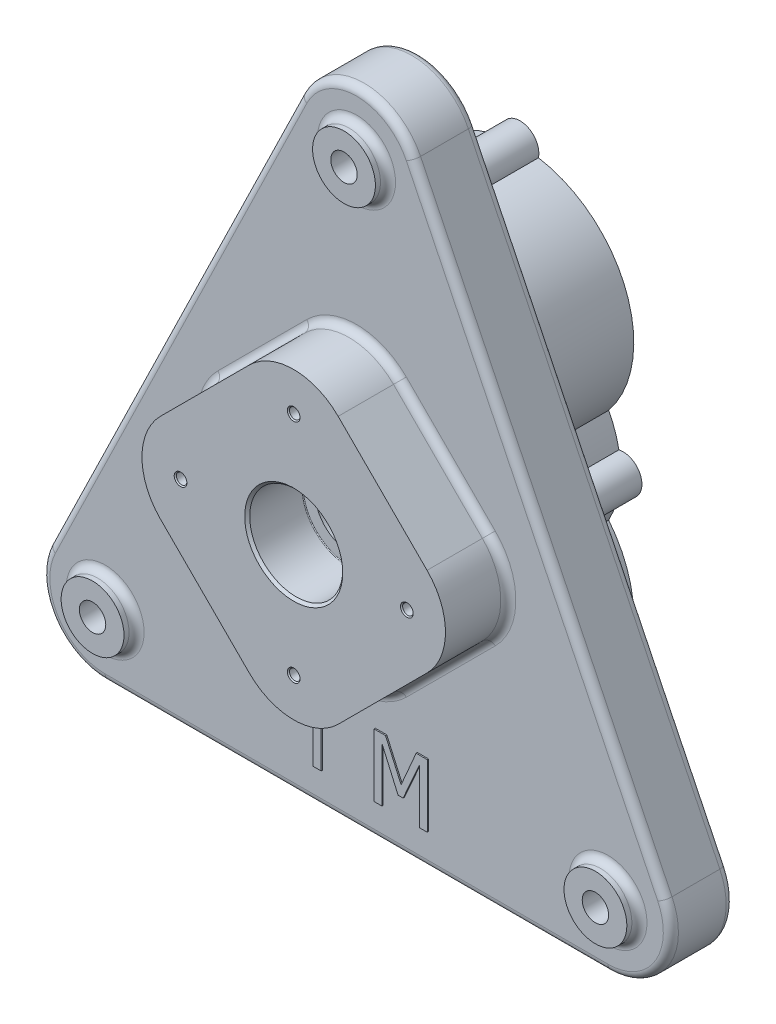
SolidWorks part; units mm, degrees
material "Cast Alloy Steel"
ref_plane "Front Plane" through (0, 0, 0) normal (0, 0, 1) x (1, 0, 0)
ref_plane "Top Plane" through (0, 0, 0) normal (0, 1, 0) x (1, 0, 0)
ref_plane "Right Plane" through (0, 0, 0) normal (1, 0, 0) x (0, 0, -1)
sketch "Sketch1" plane through (0, 0, 0) normal (0, 0, 1) x (1, 0, 0)
  line L0 (0, 120) -> (0, -143.1186) construction
  line L1 (-150.0941, 0) -> (143.2063, 0) construction
  line L2 (53.033, -17.6777) -> (17.6777, -53.033)
  line L3 (53.033, 17.6777) -> (17.6777, 53.033)
  line L4 (-17.6777, -53.033) -> (-53.033, -17.6777)
  line L5 (-17.6777, 53.033) -> (-53.033, 17.6777)
  line L6 (70.7107, 0) -> (-70.7107, 0) construction
  line L7 (0, -70.7107) -> (0, 70.7107) construction
  line L8 (-22.4692, 130.9606) -> (-122.4692, -74.0394)
  line L9 (-100, -110) -> (100, -110)
  line L10 (122.4692, -74.0394) -> (22.4692, 130.9606)
  circle A0 centre (0, 0) radius 13.5
  circle A1 centre (0, 120) radius 12.5
  circle A3 centre (-100, -85) radius 12.5
  circle A4 centre (100, -85) radius 12.5
  arc A5 (22.4692, 130.9606) -> (-22.4692, 130.9606) centre (0, 120) ccw
  arc A6 (-122.4692, -74.0394) -> (-100, -110) centre (-100, -85) ccw
  arc A7 (100, -110) -> (122.4692, -74.0394) centre (100, -85) ccw
  arc A8 (-53.033, -17.6777) -> (-53.033, 17.6777) centre (-35.3553, 0) cw
  arc A9 (17.6777, -53.033) -> (-17.6777, -53.033) centre (0, -35.3553) cw
  arc A10 (53.033, 17.6777) -> (53.033, -17.6777) centre (35.3553, 0) cw
  arc A11 (17.6777, 53.033) -> (-17.6777, 53.033) centre (0, 35.3553) ccw
  circle A12 centre (0, 120) radius 5.25
  circle A13 centre (-100, -85) radius 5.25
  circle A14 centre (100, -85) radius 5.25
  dimension "D1" = 25
  dimension "D7" = 27
  dimension "D8" = 50
  dimension "D9" = 25
  dimension "D10" = 10.5
  dimension "D2" = 120
  dimension "D3" = 205
  dimension "D4" = 100
  dimension "D5" = 100
  dimension "D6" = 100
extrude "Boss-Extrude1" add sketch "Sketch1" along normal blind 25 contours L9 A7 L10 A5 L8 A6 A11 L3 A10 L2 A9 L4 A8 L5 A4 A3 A1 | L3 A11 L5 A8 L4 A9 L2 A10 A0 | A4 A14 | A1 A12 | A3 A13 region at (34.1482, -34.1482, 0) region at (0, 141.4289, 0) region at (-12.1464, 120, 0) region at (-112.1464, -85, 0) region at (87.8536, -85, 0)
extrude "Boss-Extrude2" add sketch "Sketch1<3>" along normal blind 50 contours L3 A11 L5 A8 L4 A9 L2 A10 A0 region at (34.1482, -34.1482, 0)
sketch "Sketch1<3>" plane through (0, 0, 0) normal (0, 0, 1) x (1, 0, 0) same geometry as "Sketch1"
sketch "Sketch2" plane through (0, 0, 0) normal (0, 0, -1) x (-1, 0, 0)
  line L0 (0, 145) -> (0, -110) construction
  line L1 (100, -110) -> (-100, -110) construction
  line L2 (-86.3524, 0) -> (86.3524, 0) construction
  line L3 (-122.4692, -74.0394) -> (-22.4692, 130.9606) construction
  line L4 (22.4692, 130.9606) -> (122.4692, -74.0394) construction
  arc A0 (22.4692, 130.9606) -> (-22.4692, 130.9606) centre (0, 120) ccw construction
  arc A1 (-28.1448, 12.9949) -> (-28.1448, -12.9949) centre (0, 0) ccw
  arc A2 (-32.4459, 13.125) -> (-32.4459, -13.125) centre (0, 0) ccw
  arc A3 (-35.2592, 18.8889) -> (-39.3262, 7.3108) centre (0, 0) ccw
  arc A4 (29.403, 26.0479) -> (-29.403, 26.0479) centre (0, 47.25) ccw
  arc A5 (33.634, 25.1408) -> (-33.634, 25.1408) centre (0, 47.25) ccw
  arc A6 (35.2592, 18.8889) -> (7.3279, 91.9027) centre (0, 47.25) ccw
  arc A7 (7.3279, 91.9027) -> (-7.3279, 91.9027) centre (0, 93.5) ccw
  arc A8 (-7.3279, 91.9027) -> (-35.2592, 18.8889) centre (0, 47.25) ccw
  arc A9 (29.403, -26.0479) -> (-29.403, -26.0479) centre (0, -47.25) cw
  arc A10 (33.634, -25.1408) -> (-33.634, -25.1408) centre (0, -47.25) cw
  arc A11 (35.2592, -18.8889) -> (7.3279, -91.9027) centre (0, -47.25) cw
  arc A12 (-7.3279, -91.9027) -> (-35.2592, -18.8889) centre (0, -47.25) cw
  arc A13 (7.3279, -91.9027) -> (-7.3279, -91.9027) centre (0, -93.5) cw
  arc A14 (28.1448, -12.9949) -> (28.1448, 12.9949) centre (0, 0) ccw
  arc A15 (32.4459, -13.125) -> (32.4459, 13.125) centre (0, 0) ccw
  arc A16 (35.2592, -18.8889) -> (39.3262, -7.3108) centre (0, 0) ccw
  arc A17 (-39.3262, 7.3108) -> (-39.3262, -7.3108) centre (-41, 0) ccw
  arc A18 (39.3262, 7.3108) -> (39.3262, -7.3108) centre (41, 0) cw
  arc A19 (-39.3262, -7.3108) -> (-35.2592, -18.8889) centre (0, 0) ccw
  arc A20 (39.3262, 7.3108) -> (35.2592, 18.8889) centre (0, 0) ccw
  arc A21 (33.634, -25.1408) -> (32.4459, -13.125) centre (44.4972, -18) cw
  arc A22 (29.403, -26.0479) -> (28.1448, -12.9949) centre (39.9475, -18.4444) cw
  arc A23 (32.4459, 13.125) -> (33.634, 25.1408) centre (44.4972, 18) cw
  arc A24 (29.403, 26.0479) -> (28.1448, 12.9949) centre (39.9475, 18.4444) ccw
  arc A25 (-33.634, -25.1408) -> (-32.4459, -13.125) centre (-44.4972, -18) ccw
  arc A26 (-29.403, -26.0479) -> (-28.1448, -12.9949) centre (-39.9475, -18.4444) ccw
  arc A27 (-33.634, 25.1408) -> (-32.4459, 13.125) centre (-44.4972, 18) cw
  arc A28 (-29.403, 26.0479) -> (-28.1448, 12.9949) centre (-39.9475, 18.4444) cw
  point P43 (29.1018, -19.4444)
  point P46 (23.7788, -19.8889)
  point P49 (29.1018, 19.4444)
  point P52 (23.7788, 19.8889)
  point P55 (-29.1018, -19.4444)
  point P58 (-23.7788, -19.8889)
  point P61 (-29.1018, 19.4444)
  point P64 (-23.7788, 19.8889)
  circle M31 centre (0, 0) radius 13.5
  dimension "D1" = 62
  dimension "D2" = 70
  dimension "D3" = 80
  dimension "D5" = 72.5
  dimension "D6" = 80.5
  dimension "D7" = 90.5
  dimension "D8" = 15
  dimension "D11" = 13
  dimension "D4" = 47.25
  dimension "D9" = 93.5
  dimension "D10" = 41
extrude "Boss-Extrude4" add sketch "Sketch2" along normal blind 40 contours A18 A20 A6 A7 A8 A3 A17 A19 A12 A13 A11 A16 A27 A5 A23 A15 A21 A10 A25 A2 region at (40.1702, 62.617, 0)
extrude "Boss-Extrude5" add sketch "Sketch2<6>" along normal blind 35 contours A5 A27 A2 A25 A10 A21 A15 A23 A28 A4 A24 A14 A22 A9 A26 A1 region at (29.6434, 19.4688, 0)
sketch "Sketch2<6>" plane through (0, 0, 0) normal (0, 0, -1) x (-1, 0, 0) same geometry as "Sketch2"
sketch "Sketch4" plane through (0, 0, 0) normal (0, 0, -1) x (-1, 0, 0)
  line L0 (0, 101) -> (0, -101) construction
  line L1 (-48.5, 0) -> (48.5, 0) construction
  circle A0 centre (0, 47.25) radius 15
  arc A1 (7.3279, 91.9027) -> (-7.3279, 91.9027) centre (0, 93.5) ccw construction
  arc A2 (-7.3279, -91.9027) -> (7.3279, -91.9027) centre (0, -93.5) ccw construction
  arc A3 (-39.3262, 7.3108) -> (-39.3262, -7.3108) centre (-41, 0) ccw construction
  arc A4 (39.3262, -7.3108) -> (39.3262, 7.3108) centre (41, 0) ccw construction
  circle A5 centre (0, 47.25) radius 12
  circle A6 centre (0, -47.25) radius 12
  circle A7 centre (0, -47.25) radius 15
  dimension "D1" = 30
  dimension "D2" = 24
extrude "Cut-Extrude6" cut sketch "Sketch2<7>" against normal blind 5 contours A4 A28 A1 A26 A9 A22 A14 A24 M31 region at (25.1953, 19.8664, 0)
sketch "Sketch2<7>" plane through (0, 0, 0) normal (0, 0, -1) x (-1, 0, 0) same geometry as "Sketch2"
extrude "Cut-Extrude7" cut sketch "Sketch4" against normal blind 20 contours A6 | A5 region at (0, 47.25, 0) region at (0, -47.25, 0)
extrude "Cut-Extrude8" cut sketch "Sketch4<5>" against normal blind 18 contours A0 A5 | A7 A6 region at (14.5757, 47.25, 0) region at (14.5757, -47.25, 0)
sketch "Sketch4<5>" plane through (0, 0, 0) normal (0, 0, -1) x (-1, 0, 0) same geometry as "Sketch4"
sketch "Sketch5" plane through (0, 0, 5) normal (0, 0, -1) x (-1, 0, 0)
  circle A0 centre (0, 0) radius 18.5
  dimension "D1" = 37
extrude "Cut-Extrude9" cut sketch "Sketch5" against normal blind 17
extrude "Cut-Extrude10" cut sketch "Sketch5<2>" along normal blind 22 from surface starting at face at (13.5, 0, 50)
sketch "Sketch5<2>" plane through (0, 0, 5) normal (0, 0, -1) x (-1, 0, 0) same geometry as "Sketch5"
fillet "Fillet1" radius 3 28 edges at (-27.0075, 19.6917, 5) (-31, 0, 5) (-27.0075, -19.6917, 5) (0, -83.5, 5) (27.0075, -19.6917, 5) (31, 0, 5) (27.0075, 19.6917, 5) (0, 60.3553, 25) (-35.3553, 35.3553, 25) (-60.3553, 0, 25) (-35.3553, -35.3553, 25) (0, -60.3553, 25) (35.3553, -35.3553, 25) (60.3553, 0, 25) (121.2016, -98.2474, 25) (0, -110, 25) (-121.2016, -98.2474, 25) (-72.4692, 28.4606, 25) (0, 145, 25) (121.2016, -98.2474, 0) (0, -110, 0) (-121.2016, -98.2474, 0) (-72.4692, 28.4606, 0) (0, 145, 0) (0, 83.5, 5) (35.3553, 35.3553, 25) (72.4692, 28.4606, 25) (72.4692, 28.4606, 0)
sketch "Sketch6" plane through (0, 0, 50) normal (0, 0, 1) x (1, 0, 0)
  circle A0 centre (0, 0) radius 45 construction
  circle A1 centre (0, 45) radius 3.6648
  circle A2 centre (45, 0) radius 3.6648
  circle A3 centre (0, -45) radius 3.6648
  circle A4 centre (-45, 0) radius 3.6648
  point P5 (-45, 0)
  point P14 (0, 0)
  dimension "D1" = 90
  dimension "D2" = 7.3295
  dimension "D3" = 4
hole_wizard "M5x0.8 Tapped Hole1" positions "3DSketch1" profile "Sketch7" tap size "M5x0.8" standard "ANSI Metric"
sketch3d "3DSketch1"
  point P0 (0, 45, 50)
  point P3 (-45, 0, 50)
  point P6 (45, 0, 50)
  point P9 (0, -45, 50)
sketch "Sketch7" plane through (0, 45, 50) normal (1, 0, 0) x (0, -1, 0)
  line L0 (0, 0) -> (0, 15)
  line L1 (0, 15) -> (2.1, 13.7382)
  line L2 (2.1, 13.7382) -> (2.1, 0.425)
  line L3 (2.1, 0.425) -> (2.525, 0)
  line L5 (2.525, 0) -> (0, 0)
  line L6 (-2.1, 0.425) -> (-2.525, 0) construction
  line L10 (0, 15) -> (-2.1, 13.7382) construction
  line L11 (0, -6.35) -> (0, 107.95) construction
  dimension "Tap Drill Dia." = 4.2
  dimension "Tap Drill Depth" = 15
  dimension "Near C'Sink Dia." = 5.05
  dimension "Near C'Sink Angle" = 90
  dimension "Drill Angle" = 118
cosmetic thread "Hole Thread1" parameters "D1"=13, "D2"=5
cosmetic thread "Hole Thread2" parameters "D1"=13, "D2"=5
cosmetic thread "Hole Thread3" parameters "D1"=13, "D2"=5
cosmetic thread "Hole Thread4" parameters "D1"=13, "D2"=5
sketch "Sketch8" plane through (0, 0, -40) normal (0, 0, -1) x (-1, 0, 0)
  circle A0 centre (0, 93.5) radius 2.5
  circle A1 centre (41, 0) radius 2.5
  circle A2 centre (-41, 0) radius 2.5
  circle A3 centre (0, -93.5) radius 2.5
  point P12 (-41, 0)
  point P13 (-41, 0)
  dimension "D1" = 5
  dimension "D2" = 5
hole_wizard "M6x1.0 Tapped Hole1" positions "3DSketch2" profile "Sketch9" tap size "M6x1.0" standard "ANSI Metric"
sketch3d "3DSketch2"
  point P0 (0, 93.5, -40)
  point P3 (-41, 0, -40)
  point P6 (41, 0, -40)
  point P9 (0, -93.5, -40)
sketch "Sketch9" plane through (0, 93.5, -40) normal (1, 0, 0) x (0, 1, 0)
  line L0 (0, 0) -> (0, 22)
  line L1 (0, 22) -> (2.5, 20.4978)
  line L2 (2.5, 20.4978) -> (2.5, 0.525)
  line L3 (2.5, 0.525) -> (3.025, 0)
  line L5 (3.025, 0) -> (0, 0)
  line L6 (-2.5, 0.525) -> (-3.025, 0) construction
  line L10 (0, 22) -> (-2.5, 20.4978) construction
  line L11 (0, -6.35) -> (0, 107.95) construction
  dimension "Tap Drill Dia." = 5
  dimension "Tap Drill Depth" = 22
  dimension "Near C'Sink Dia." = 6.05
  dimension "Near C'Sink Angle" = 90
  dimension "Drill Angle" = 118
cosmetic thread "Hole Thread5" parameters "D1"=20, "D2"=6
cosmetic thread "Hole Thread6" parameters "D1"=20, "D2"=6
cosmetic thread "Hole Thread7" parameters "D1"=20, "D2"=6
cosmetic thread "Hole Thread8" parameters "D1"=20, "D2"=6
fillet "Fillet3" radius 2 12 edges at (37.7393, -13.2568, 0) (37.7393, 13.2568, 0) (48.5, 0, 0) (0, 101, 0) (42.2631, 63.4176, 0) (-37.7393, -13.2568, 0) (-37.7393, 13.2568, 0) (-42.2631, 63.4176, 0) (-48.5, 0, 0) (0, -101, 0) (42.2631, -63.4176, 0) (-42.2631, -63.4176, 0)
chamfer "Chamfer1" distance 1 angle 45 4 edges at (18.5, 0, 50) (-15, -47.25, 5) (-15, 47.25, 5) (-18.5, 0, 5)
sketch "Sketch10" plane through (0, 0, 25) normal (0, 0, 1) x (1, 0, 0)
  line L0 (-100, -107) -> (100, -107) construction
  text T0 "TM" font "Tahoma" height 25
  point P1 (-28.3234, -87.0645)
  point P2 (-27.0426, -90.5865)
  dimension "D1" = 10
  dimension "D2" = 25
extrude "Boss-Extrude6" add sketch "Sketch10" along normal blind 0.5
sketch "Sketch11" plane through (0, 0, 25) normal (0, 0, 1) x (1, 0, 0)
  circle A0 centre (0, 120) radius 12.5
  circle A1 centre (100, -85) radius 12.5
  circle A2 centre (-100, -85) radius 12.5
  circle A15 centre (100, -85) radius 5.25
  circle A16 centre (0, 120) radius 5.25
  circle A17 centre (-100, -85) radius 5.25
  dimension "D1" = 25
  dimension "D2" = 10.5
extrude "Boss-Extrude7" add sketch "Sketch11" along normal blind 5
fillet "Fillet5" radius 3 3 edges at (12.5, 120, 25) (-87.5, -85, 25) (112.5, -85, 25)
sketch "Sketch12" plane through (0, 0, 0) normal (0, 0, -1) x (-1, 0, 0)
  circle A0 centre (0, 120) radius 12
  circle A1 centre (100, -85) radius 12
  circle A2 centre (-100, -85) radius 12
  dimension "D1" = 24
extrude "Cut-Extrude11" cut sketch "Sketch12" against normal blind 0.8
fillet "Fillet6" radius 3 2 edges at (-12, -47.25, 20) (-12, 47.25, 20)
fillet "Fillet7" radius 0.3 2 edges at (-15, -47.25, 18) (-15, 47.25, 18)
fillet "Fillet8" radius 0.3 2 edges at (18.5, 0, 28) (-18.5, 0, 22)
chamfer "Chamfer3" distance 1 angle 45 3 edges at (88, -85, 0.8) (-112, -85, 0.8) (-12, 120, 0.8)
